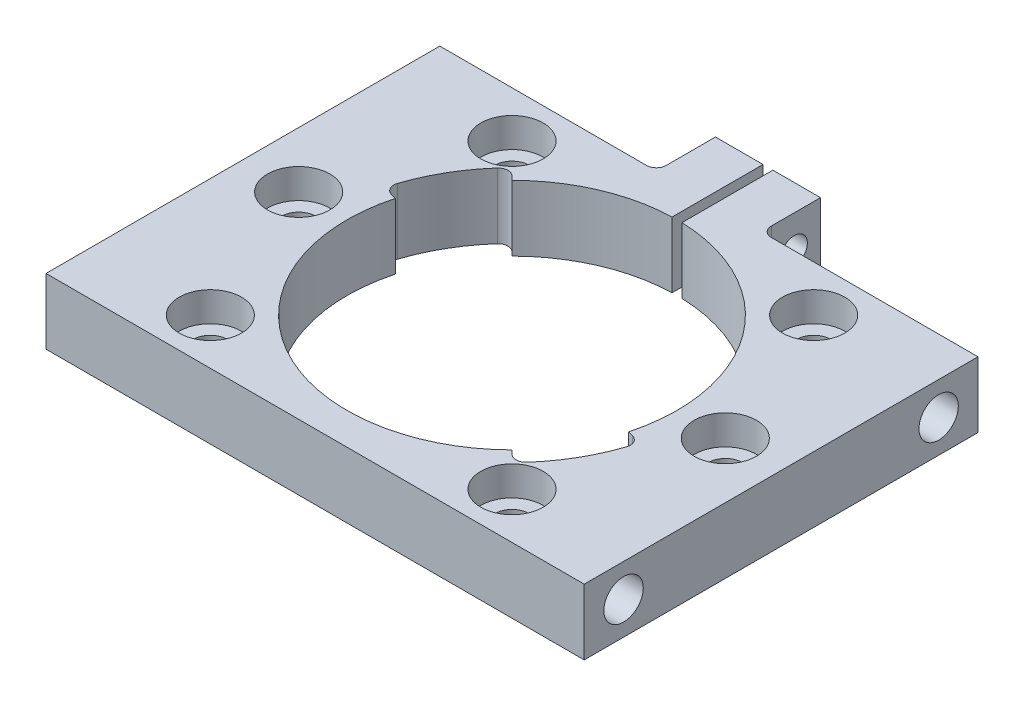
SolidWorks part; units mm, degrees
material "6061 Alloy"
ref_plane "Front Plane" through (0, 0, 0) normal (0, 0, 1) x (1, 0, 0)
ref_plane "Top Plane" through (0, 0, 0) normal (0, 1, 0) x (1, 0, 0)
ref_plane "Right Plane" through (0, 0, 0) normal (1, 0, 0) x (0, 0, -1)
sketch "Sketch1" plane through (0, 76, 0) normal (0, 1, 0) x (1, 0, 0)
  line L0 (-18.3542, 18.3542) -> (18.3542, -18.3542)
  line L1 (-41, -30) -> (41, -30)
  line L2 (-41, -30) -> (-41, 30)
  line L3 (-41, 30) -> (41, 30)
  line L4 (41, -30) -> (41, 30)
  line L5 (-41, -30) -> (41, 30) construction
  line L6 (-41, 30) -> (41, -30) construction
  line L7 (-25.0722, 6.7181) -> (25.0722, -6.7181)
  line L8 (-103.759, 0) -> (103.759, 0) construction
  circle A0 centre (0, 0) radius 25.15
  arc A1 (-20.5349, 18.2912) -> (-26.1081, 8.6381) centre (0, 0) ccw
  arc A2 (26.1081, -8.6381) -> (20.5349, -18.2912) centre (0, 0) cw
  circle A3 centre (0, 0) radius 27.5 construction
  arc A4 (18.3542, -18.3542) -> (20.5349, -18.2912) centre (19.4148, -17.2935) ccw
  arc A5 (25.0722, -6.7181) -> (26.1081, -8.6381) centre (24.684, -8.167) cw
  arc A6 (-25.0722, 6.7181) -> (-26.1081, 8.6381) centre (-24.684, 8.167) cw
  arc A7 (-18.3542, 18.3542) -> (-20.5349, 18.2912) centre (-19.4148, 17.2935) ccw
  circle A8 centre (22.981, 22.981) radius 2 construction
  circle A9 centre (32.5, 0) radius 2 construction
  circle A10 centre (22.981, -22.981) radius 2 construction
  circle A11 centre (-22.981, -22.981) radius 2 construction
  circle A12 centre (-32.5, 0) radius 2 construction
  circle A13 centre (-22.981, 22.981) radius 2 construction
  circle A14 centre (22.981, 22.981) radius 2
  circle A15 centre (32.5, 0) radius 2
  circle A16 centre (22.981, -22.981) radius 2
  circle A17 centre (-22.981, -22.981) radius 2
  circle A18 centre (-32.5, 0) radius 2
  circle A19 centre (-22.981, 22.981) radius 2
  point P0 (0, 0)
  dimension "D1" = 50.3
  dimension "D4" = 1.5
  dimension "D2" = 45
  dimension "D3" = 15
  dimension "D5" = 82
  dimension "D6" = 60
extrude "Boss-Extrude1" add sketch "Sketch1" along normal blind 10 contours L1 L4 L3 L2 A19 A18 A17 A16 A15 A14 A7 L0 A0 L7 A5 A2 A4 A6 A1 region at (-39.9839, 76, 0)
sketch "Sketch2" plane through (0, 86, 0) normal (0, 1, 0) x (1, 0, 0)
  line L0 (0, -142.3844) -> (0, 142.3844) construction
  line L1 (-8, 39) -> (8, 39)
  line L2 (-8, 39) -> (-8, 30)
  line L3 (-8, 30) -> (8, 30)
  line L4 (8, 39) -> (8, 30)
  line L5 (-8, 39) -> (8, 30) construction
  line L6 (-8, 30) -> (8, 39) construction
  line L7 (-41, 30) -> (41, 30) construction
  point P0 (0, 34.5)
  dimension "D1" = 9
  dimension "D2" = 16
extrude "Boss-Extrude2" add sketch "Sketch2" against normal blind 10
sketch "Sketch3" plane through (0, 86, 0) normal (0, 1, 0) x (1, 0, 0)
  line L0 (0, -142.3844) -> (0, 142.3844) construction
  line L1 (-0.75, 25) -> (0.75, 25)
  line L2 (-0.75, 25) -> (-0.75, 39)
  line L3 (-0.75, 39) -> (0.75, 39)
  line L4 (0.75, 25) -> (0.75, 39)
  line L5 (-0.75, 25) -> (0.75, 39) construction
  line L6 (-0.75, 39) -> (0.75, 25) construction
  line L7 (8, 39) -> (-8, 39) construction
  point P0 (0, 32)
  dimension "D1" = 14
  dimension "D2" = 1.5
extrude "Cut-Extrude1" cut sketch "Sketch3" against normal blind 10
sketch "Sketch4" plane through (8, 0, 0) normal (1, 0, 0) x (0, 0, -1)
  line L0 (35, 81) -> (39, 81) construction
  line L1 (39, 76) -> (39, 86) construction
  circle A0 centre (35, 81) radius 2
  dimension "D1" = 4
  dimension "D2" = 4
extrude "Cut-Extrude2" cut sketch "Sketch4" against normal up to vertex (7.25 mm away) up to point (0.75, 86, -39)
sketch "Sketch5" plane through (-0.75, 0, 0) normal (1, 0, 0) x (0, 0, -1)
  circle A0 centre (35, 81) radius 1.6
  dimension "D1" = 3.2
extrude "Cut-Extrude3" cut sketch "Sketch5" against normal blind 10
sketch "Sketch7" plane through (0, 86, 0) normal (0, 1, 0) x (1, 0, 0)
  circle A0 centre (-22.981, 22.981) radius 4.75
  circle A1 centre (22.981, 22.981) radius 4.75
  circle A2 centre (32.5, 0) radius 4.75
  circle A3 centre (-32.5, 0) radius 4.75
  circle A4 centre (-22.981, -22.981) radius 4.75
  circle A5 centre (22.981, -22.981) radius 4.75
  dimension "D1" = 9.5
extrude "Cut-Extrude4" cut sketch "Sketch7" against normal blind 4.5
fillet "Fillet1" radius 1.5 2 edges at (-8, 81, -30) (8, 81, -30)
sketch "Sketch8" plane through (0, 86, 0) normal (0, 1, 0) x (1, 0, 0)
  line L0 (9.4279, 0) -> (0, 0) construction
  line L1 (-41, 30) -> (-29, 30)
  line L2 (-41, 30) -> (-41, 18)
  line L3 (-41, 18) -> (-29, 18)
  line L4 (-29, 30) -> (-29, 18)
  line L5 (0, 0) -> (0, 11.3596) construction
  line L6 (29, 30) -> (29, 18)
  line L7 (41, 18) -> (29, 18)
  line L8 (41, 30) -> (41, 18)
  line L9 (41, 30) -> (29, 30)
  line L10 (41, -30) -> (29, -30)
  line L11 (41, -30) -> (41, -18)
  line L12 (41, -18) -> (29, -18)
  line L13 (29, -30) -> (29, -18)
  line L14 (-29, -30) -> (-29, -18)
  line L15 (-41, -18) -> (-29, -18)
  line L16 (-41, -30) -> (-41, -18)
  line L17 (-41, -30) -> (-29, -30)
  dimension "D1" = 12
  dimension "D2" = 12
extrude "Boss-Extrude3" add sketch "Sketch8" along normal blind 10
fillet "Fillet2" radius 1.5 8 edges at (35, 86, 18) (-35, 86, 18) (-29, 86, 24) (29, 86, 24) (29, 86, -24) (35, 86, -18) (-35, 86, -18) (-29, 86, -24)
sketch "Sketch9" plane through (-41, 0, 0) normal (-1, 0, 0) x (0, 0, 1)
  line L0 (0, 86) -> (0, 76) construction
  line L1 (16.5, 86) -> (-16.5, 86) construction
  line L2 (30, 76) -> (-30, 76) construction
  line L3 (-30, 96) -> (-18, 96) construction
  line L4 (-30, 96) -> (-30, 76) construction
  circle A0 centre (-24, 91) radius 3
  circle A1 centre (-24, 81) radius 3
  circle A2 centre (24, 81) radius 3
  circle A3 centre (24, 91) radius 3
  dimension "D2" = 6
  dimension "D3" = 6
  dimension "D4" = 5
  dimension "D5" = 6
  dimension "D1" = 5
extrude "Cut-Extrude5" cut sketch "Sketch9" against normal blind 12
mirror "Mirror1" about plane through (0, 0, 0) normal (1, 0, 0) of "Cut-Extrude5"
sketch "Sketch10" plane through (0, 86, 0) normal (0, 1, 0) x (1, 0, 0)
  line L1 (-41, 30) -> (41, 30)
  line L2 (-41, 30) -> (-41, -30)
  line L3 (-41, -30) -> (41, -30)
  line L4 (41, 30) -> (41, -30)
extrude "Cut-Extrude6" cut sketch "Sketch10" along normal up to vertex (10 mm away) up to point (-41, 96, -30)
sketch "Sketch11" plane through (0, 81.5, 0) normal (0, 1, 0) x (1, 0, 0)
  circle A0 centre (-22.981, 22.981) radius 2.6
  circle A1 centre (22.981, 22.981) radius 2.6
  circle A2 centre (-32.5, 0) radius 2.6
  circle A3 centre (-22.981, -22.981) radius 2.6
  circle A4 centre (32.5, 0) radius 2.6
  circle A5 centre (22.981, -22.981) radius 2.6
  dimension "D1" = 5.2
extrude "Cut-Extrude7" cut sketch "Sketch11" against normal blind 10
